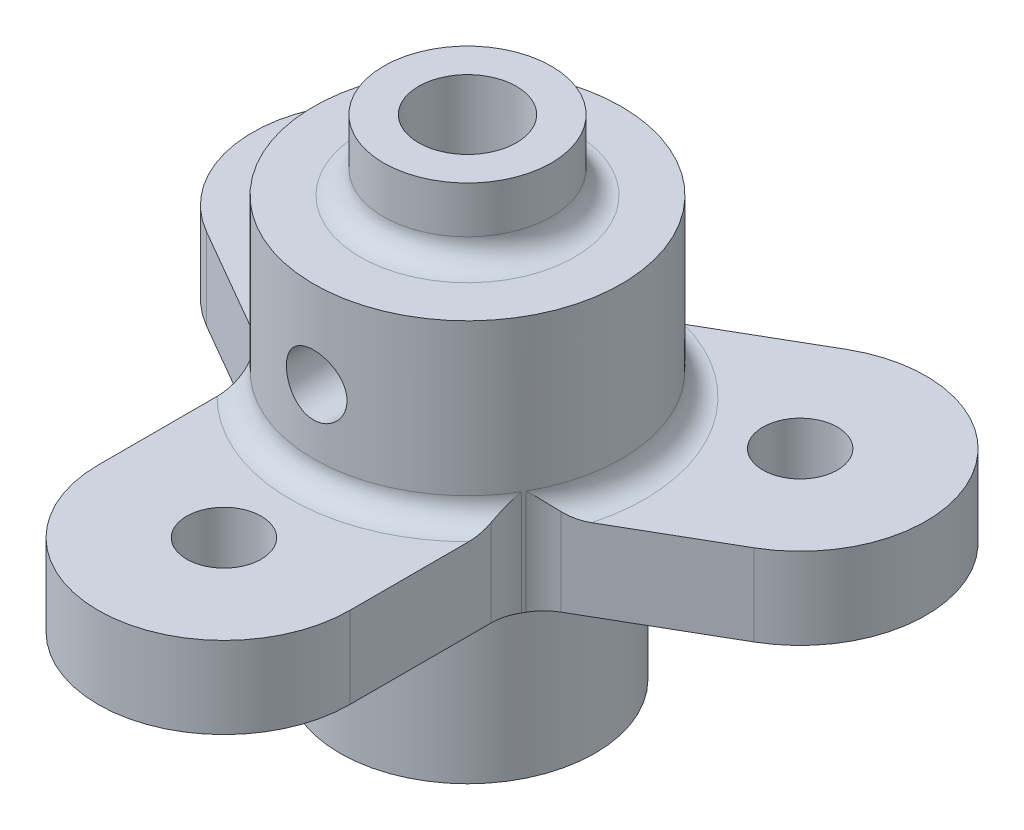
SolidWorks part; units mm, degrees
ref_plane "Front Plane" through (0, 0, 0) normal (0, 0, 1) x (1, 0, 0)
ref_plane "Top Plane" through (0, 0, 0) normal (0, 1, 0) x (1, 0, 0)
ref_plane "Right Plane" through (0, 0, 0) normal (1, 0, 0) x (0, 0, -1)
sketch "Sketch1" plane through (0, 0, 0) normal (0, 1, 0) x (1, 0, 0)
  circle A0 centre (0, 0) radius 2.1
  circle A1 centre (0, 0) radius 3.6
  dimension "D1" = 4.2
  dimension "D2" = 1.5
extrude "Boss-Extrude1" add sketch "Sketch1" along normal blind 3
sketch "Sketch2" plane through (0, 0, 0) normal (0, -1, 0) x (1, 0, 0)
  circle A0 centre (0, 0) radius 2.1
  circle A1 centre (0, 0) radius 6.6
  circle A2 centre (0, 0) radius 2.1 construction
  dimension "D1" = 4.5
  dimension "0" = 0
extrude "Boss-Extrude2" add sketch "Sketch2" along normal blind 11
sketch "Sketch3" plane through (0, -11, 0) normal (0, -1, 0) x (1, 0, 0)
  line L0 (0, 0) -> (0, 50000) construction
  line L1 (0, 0) -> (50000, 0) construction
  line L2 (-5.4, 10.45) -> (-5.4, 3.7947)
  line L3 (5.4, 10.45) -> (5.4, 3.7947)
  circle A1 centre (0, 0) radius 6.6 construction
  circle A2 centre (0, 0) radius 21.6 construction
  circle A3 centre (0, 10.45) radius 1.6 construction
  arc A4 (5.4, 10.45) -> (-5.4, 10.45) centre (0, 10.45) ccw
  circle A6 centre (0, 10.45) radius 1.6
  arc A7 (5.4, 3.7947) -> (-5.4, 3.7947) centre (0, 0) ccw
  dimension "D1" = 43.2
  dimension "D2" = 3.2
  dimension "D4" = 3.8
  dimension "D3" = 10.45
extrude "Boss-Extrude3" add sketch "Sketch3" against normal blind 3.5
pattern_circular "CirPattern1" count 3 over 360 about axis through (0, 3, 0) along (0, -1, 0) of "Boss-Extrude3" reverse direction yes
sketch "Sketch4" plane through (0, 0, 0) normal (0, 0, 1) x (1, 0, 0)
  line L0 (0, 0) -> (0, -7.5) construction
  line L1 (5.4, -7.5) -> (-5.4, -7.5) construction
  line L2 (-6.6, -3.75) -> (6.6, -3.75) construction
  line L3 (6.6, -7.5) -> (6.6, 0) construction
  circle A0 centre (0, -3.75) radius 1.3
  point P10 (0, -3.75)
  dimension "D1" = 2.6
extrude "Cut-Extrude1" cut sketch "Sketch4" against normal mid plane 15
sketch "Sketch5" plane through (0, -11, 0) normal (0, -1, 0) x (1, 0, 0)
  circle A0 centre (0, 10.45) radius 2
  circle A1 centre (0, 10.45) radius 1.6
  circle A2 centre (0, 10.45) radius 1.6 construction
  dimension "D1" = 4
extrude "Boss-Extrude4" [suppressed] add sketch "Sketch5" along normal blind 3
pattern_circular "CirPattern2" [suppressed] count 3 over 360 reverse direction yes of bodies 106
fillet "Fillet1" radius 2 6 edges at (0.5863, -9.25, -6.5739) (-0.5863, -9.25, -6.5739) (5.4, -9.25, 3.7947) (5.9863, -9.25, 2.7792) (-5.9863, -9.25, 2.7792) (-5.4, -9.25, 3.7947)
fillet "Fillet2" radius 1 4 edges at (0, 0, 3.6) (-5.7158, -7.5, -3.3) (5.7158, -7.5, -3.3) (0, -7.5, 6.6)
sketch "Sketch6" plane through (0, -11, 0) normal (0, -1, 0) x (1, 0, 0)
  circle A0 centre (0, 0) radius 5.475
  circle A1 centre (0, 0) radius 2.1
  circle A2 centre (0, 0) radius 2.1 construction
  dimension "D1" = 10.95
extrude "Boss-Extrude5" add sketch "Sketch6" along normal blind 7
